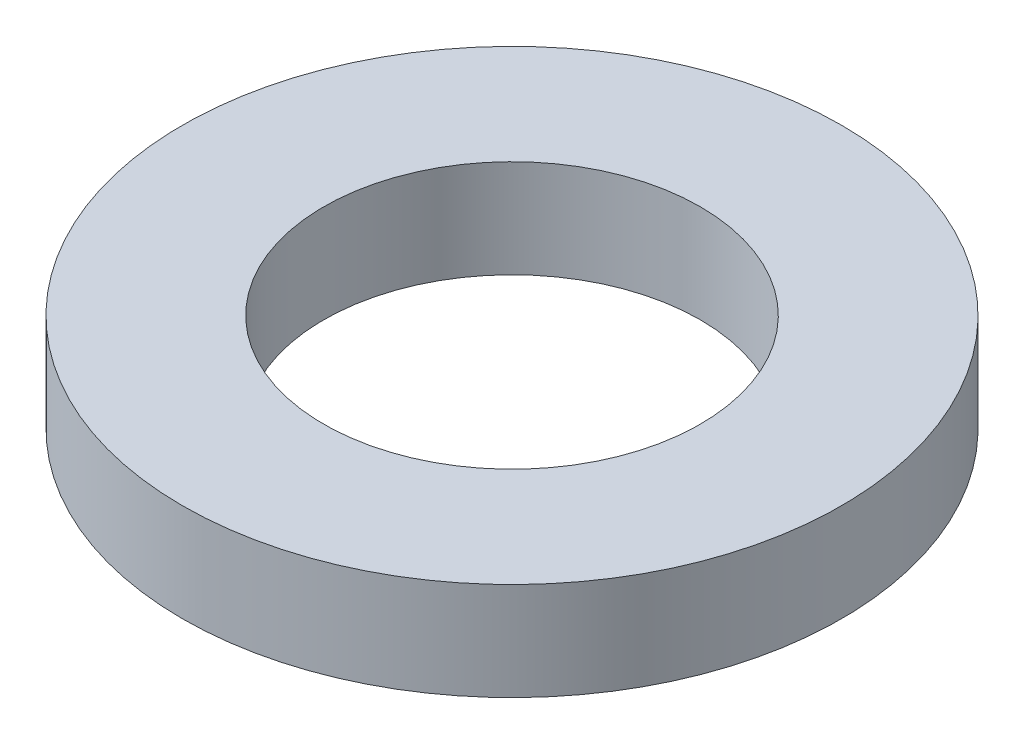
SolidWorks part; units mm, degrees
ref_plane "Front Plane" through (0, 0, 0) normal (0, 0, 1) x (1, 0, 0)
ref_plane "Top Plane" through (0, 0, 0) normal (0, 1, 0) x (1, 0, 0)
ref_plane "Right Plane" through (0, 0, 0) normal (1, 0, 0) x (0, 0, -1)
sketch "Sketch1" plane through (0, 0, 0) normal (0, 1, 0) x (1, 0, 0)
  circle A0 centre (0, 0) radius 87.5
  dimension "FLANGE_OD" = 175
extrude "Boss-Extrude1" add sketch "Sketch1" along normal blind 26
sketch "Sketch2" plane through (0, 0, 0) normal (0, 1, 0) x (1, 0, 0)
  circle A0 centre (0, 0) radius 50
  dimension "BORE_D" = 100
extrude "Cut-Extrude1" cut sketch "Sketch2" along normal through all
sketch "Sketch3" plane through (0, 26, 0) normal (0, 1, 0) x (1, 0, 0)
  circle A0 centre (0, 0) radius 34.8066 construction
  circle A1 centre (-34.8066, 0) radius 6.6399
  dimension "BOLT_D" = 13.2799
  dimension "BOLT_PCD" = 69.6131
extrude "Cut-Extrude2" cut sketch "Sketch3" against normal blind 19.8513 rebuild error yes
pattern_circular "CirPattern1" count 5 over 360 rebuild error yes
